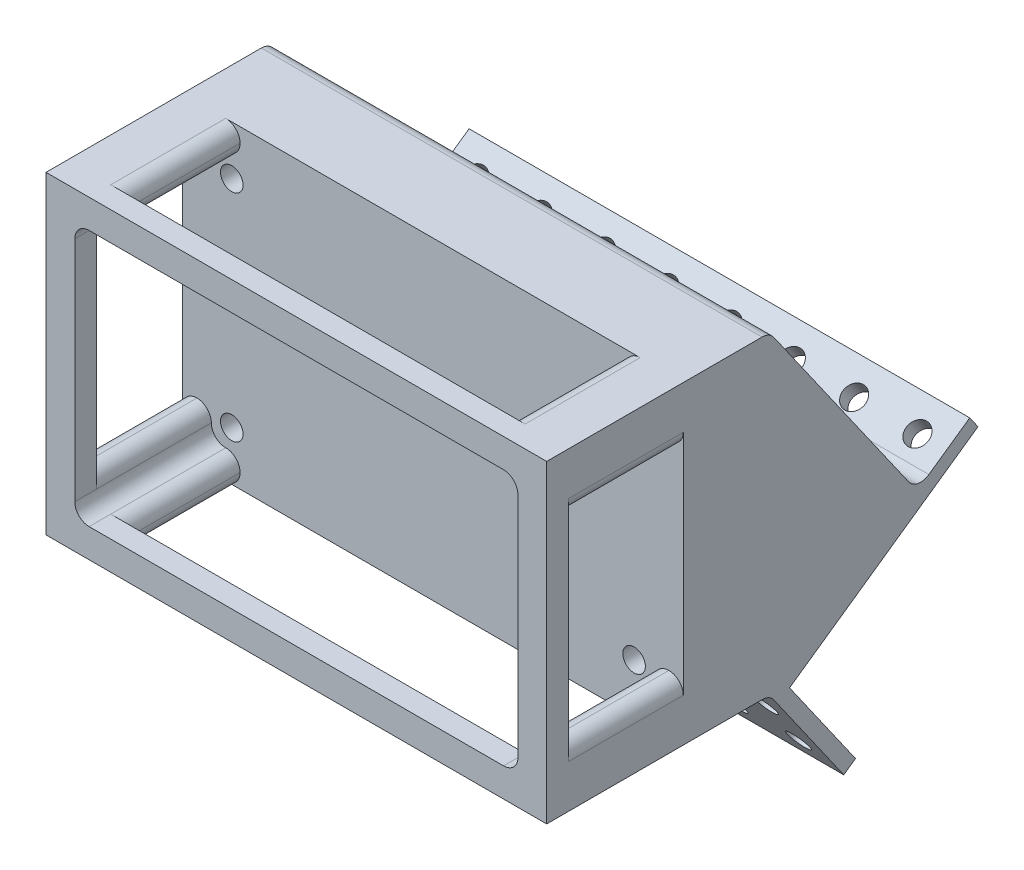
SolidWorks part; units mm, degrees
material "PET"
ref_plane "Front Plane" through (0, 0, 0) normal (0, 0, 1) x (1, 0, 0)
ref_plane "Top Plane" through (0, 0, 0) normal (0, 1, 0) x (1, 0, 0)
ref_plane "Right Plane" through (0, 0, 0) normal (1, 0, 0) x (0, 0, -1)
sketch "Sketch1" plane through (0, 0, 0) normal (0, 0, 1) x (1, 0, 0)
  line L0 (-44.4246, 23.8125) -> (-44.4246, -23.8125) construction
  line L1 (-48.9331, -28.321) -> (48.9331, -28.321)
  line L2 (-48.9331, -28.321) -> (-48.9331, 28.321)
  line L3 (-48.9331, 28.321) -> (48.9331, 28.321)
  line L4 (48.9331, -28.321) -> (48.9331, 28.321)
  line L5 (-48.9331, -28.321) -> (48.9331, 28.321) construction
  line L6 (-48.9331, 28.321) -> (48.9331, -28.321) construction
  line L7 (-55.2831, -34.671) -> (55.2831, -34.671)
  line L8 (-55.2831, -34.671) -> (-55.2831, 34.671)
  line L9 (-55.2831, 34.671) -> (55.2831, 34.671)
  line L10 (55.2831, -34.671) -> (55.2831, 34.671)
  line L11 (-55.2831, -34.671) -> (55.2831, 34.671) construction
  line L12 (-55.2831, 34.671) -> (55.2831, -34.671) construction
  line L13 (0, 28.321) -> (0, -28.321) construction
  line L14 (-55.2831, -21.971) -> (-48.9331, -21.971)
  line L15 (-48.9331, -21.971) -> (-48.9331, -28.321)
  line L16 (-48.9331, -28.321) -> (-42.5831, -28.321)
  line L17 (-42.5831, -28.321) -> (-42.5831, -34.671)
  line L18 (42.5831, -28.321) -> (42.5831, -34.671)
  line L19 (48.9331, -28.321) -> (42.5831, -28.321)
  line L20 (48.9331, -21.971) -> (48.9331, -28.321)
  line L21 (55.2831, -21.971) -> (48.9331, -21.971)
  line L22 (-55.2831, 0) -> (55.2831, 0) construction
  line L23 (55.2831, 21.971) -> (48.9331, 21.971)
  line L24 (48.9331, 21.971) -> (48.9331, 28.321)
  line L25 (48.9331, 28.321) -> (42.5831, 28.321)
  line L26 (42.5831, 28.321) -> (42.5831, 34.671)
  line L27 (-42.5831, 28.321) -> (-42.5831, 34.671)
  line L28 (-48.9331, 28.321) -> (-42.5831, 28.321)
  line L29 (-48.9331, 21.971) -> (-48.9331, 28.321)
  line L30 (-55.2831, 21.971) -> (-48.9331, 21.971)
  circle A0 centre (-44.4246, -23.8125) radius 2.4892
  circle A1 centre (-44.4246, 23.8125) radius 2.4892
  circle A2 centre (44.4246, -23.8125) radius 2.4892
  circle A3 centre (44.4246, 23.8125) radius 2.4892
  point P0 (0, 0)
  point P6 (0, 0)
  point P11 (-48.9331, 0)
  point P16 (-44.4246, 0)
  dimension "D5" = 4.9784
  dimension "D1" = 97.8662
  dimension "D2" = 56.642
  dimension "D3" = 6.35
  dimension "D4" = 6.35
  dimension "D6" = 4.5085
  dimension "D7" = 12.7
  dimension "D8" = 47.625
  dimension "D9" = 12.7
extrude "Boss-Extrude1" add sketch "Sketch1" along normal mid plane 19.05 contours L30 L8 L14 L15 L16 L17 L7 L18 L19 L20 L21 L10 L23 L24 L25 L26 L9 L27 L28 L29 A2 A1 A0 A3 | L8 L30 L29 L28 L27 L9 | L26 L25 L24 L23 L10 L9 | L10 L21 L20 L19 L18 L7 | L17 L16 L15 L14 L8 L7 | L30 L8 L14 L2 | L27 L3 L26 L9 | L10 L23 L4 L21 | L18 L1 L17 L7 | A0 | A1 | A3 | A2 region at (0, 0, 0) region at (-49.9914, -29.3793, 0) region at (0, -31.496, 0) region at (-52.1081, 0, 0) region at (49.9914, -29.3793, 0) region at (-49.9914, 29.3793, 0) region at (52.1081, 0, 0) region at (0, 31.496, 0) region at (49.9914, 29.3793, 0) region at (-44.4246, -23.8125, 0) region at (-44.4246, 23.8125, 0) region at (44.4246, -23.8125, 0) region at (44.4246, 23.8125, 0)
extrude "Boss-Extrude2" add sketch "Sketch1<3>" along normal blind 34.925 contours L8 L30 L29 L28 L27 L9 | L26 L25 L24 L23 L10 L9 | L17 L16 L15 L14 L8 L7 | L10 L21 L20 L19 L18 L7 region at (-49.9914, -29.3793, 0) region at (49.9914, -29.3793, 0) region at (-49.9914, 29.3793, 0) region at (49.9914, 29.3793, 0)
sketch "Sketch1<3>" plane through (0, 0, 0) normal (0, 0, 1) x (1, 0, 0) same geometry as "Sketch1"
extrude "Boss-Extrude3" add sketch "Sketch1<5>" along normal blind 4.7625 from surface contours L27 L3 L26 L9 | L26 L3 L4 L23 L10 L9 | L10 L23 L4 L21 | L10 L21 L4 L1 L18 L7 | L18 L1 L17 L7 | L17 L1 L2 L14 L8 L7 | L30 L8 L14 L2 | L8 L30 L2 L3 L27 L9 region at (-49.9914, -29.3793, 0) region at (0, -31.496, 0) region at (-52.1081, 0, 0) region at (49.9914, -29.3793, 0) region at (-49.9914, 29.3793, 0) region at (52.1081, 0, 0) region at (0, 31.496, 0) region at (49.9914, 29.3793, 0) starting at face at (-48.9331, 28.321, 34.925)
sketch "Sketch1<5>" plane through (0, 0, 0) normal (0, 0, 1) x (1, 0, 0) same geometry as "Sketch1"
sketch "Sketch2" plane through (0, 0, 0) normal (1, 0, 0) x (0, 0, -1)
  line L0 (9.525, 34.671) -> (9.525, -34.671)
  line L2 (9.525, 34.671) -> (42.1051, -11.8582)
  line L3 (55.5598, -6.313) -> (13.9469, -35.4507)
  line L4 (9.525, -34.671) -> (25.9149, -58.0783)
  line L5 (25.9149, -58.0783) -> (28.5158, -56.2572)
  line L6 (28.5158, -56.2572) -> (13.9469, -35.4507)
  line L8 (55.5598, -6.313) -> (53.7387, -3.7122)
  line L9 (53.7387, -3.7122) -> (42.1051, -11.8582)
  line L10 (9.525, -34.671) -> (9.525, 34.671) construction
  point P6 (9.525, 34.2254)
  dimension "D1" = 3.175
  dimension "D2" = 55
  dimension "D3" = 25.4
  dimension "D4" = 3.175
  dimension "D5" = 50.8
extrude "Boss-Extrude4" add sketch "Sketch2" along normal up to surface (55.2831 mm away) and the other way up to surface (55.2831 mm away) up to face at (55.2831, 0, 15.0813) other way up to face at (-55.2831, 0, 15.0813)
extrude "Cut-Extrude3" cut sketch "Sketch1<6>" against normal through all both and the other way through all contours A1 | A3 | A2 | A0 region at (-44.4246, -23.8125, 0) region at (-44.4246, 23.8125, 0) region at (44.4246, -23.8125, 0) region at (44.4246, 23.8125, 0)
sketch "Sketch1<6>" plane through (0, 0, 0) normal (0, 0, 1) x (1, 0, 0) same geometry as "Sketch1"
sketch "Sketch3" plane through (0, -6.9311, 9.8987) normal (0, -0.5736, 0.8192) x (1, 0, 0)
  line L0 (-55.2831, -33.8641) -> (-55.2831, -62.4391) construction
  line L1 (55.2831, -62.4391) -> (-55.2831, -62.4391) construction
  line L2 (55.2831, -62.4391) -> (55.2831, -33.8641) construction
  circle A0 centre (-48.9331, -56.0891) radius 2.4892
  circle A1 centre (-34.9522, -56.0891) radius 2.4892
  circle A2 centre (-20.9713, -56.0891) radius 2.4892
  circle A3 centre (-6.9904, -56.0891) radius 2.4892
  circle A4 centre (6.9904, -56.0891) radius 2.4892
  circle A5 centre (20.9713, -56.0891) radius 2.4892
  circle A6 centre (34.9522, -56.0891) radius 2.4892
  circle A7 centre (48.9331, -56.0891) radius 2.4892
  circle A8 centre (-34.9522, -43.3891) radius 2.4892
  circle A9 centre (-20.9713, -43.3891) radius 2.4892
  circle A10 centre (-6.9904, -43.3891) radius 2.4892
  circle A11 centre (6.9904, -43.3891) radius 2.4892
  circle A12 centre (20.9713, -43.3891) radius 2.4892
  circle A13 centre (34.9522, -43.3891) radius 2.4892
  circle A14 centre (48.9331, -43.3891) radius 2.4892
  circle A15 centre (-48.9331, -43.3891) radius 2.4892
  dimension "D3" = 4.9784
  dimension "D1" = 6.35
  dimension "D2" = 6.35
  dimension "D6" = 6.35
  dimension "D7" = 12.7
  dimension "D4" = 8
  dimension "D5" = 2
extrude "Cut-Extrude1" cut sketch "Sketch3" against normal through all both
sketch "Sketch4" plane through (0, -27.7399, -19.4237) normal (0, 0.8192, 0.5736) x (1, 0, 0)
  line L0 (55.2831, 41.891) -> (-55.2831, 41.891) construction
  line L1 (55.2831, 27.6889) -> (55.2831, 41.891) construction
  line L2 (-55.2831, 41.891) -> (-55.2831, 27.6889) construction
  circle A0 centre (48.9331, 35.541) radius 2.4892
  circle A1 centre (34.9522, 35.541) radius 2.4892
  circle A2 centre (20.9713, 35.541) radius 2.4892
  circle A3 centre (6.9904, 35.541) radius 2.4892
  circle A4 centre (-6.9904, 35.541) radius 2.4892
  circle A5 centre (-20.9713, 35.541) radius 2.4892
  circle A6 centre (-34.9522, 35.541) radius 2.4892
  circle A7 centre (-48.9331, 35.541) radius 2.4892
  dimension "D5" = 4.9784
  dimension "D1" = 6.35
  dimension "D2" = 6.35
  dimension "D4" = 6.35
  dimension "D3" = 8
extrude "Cut-Extrude2" cut sketch "Sketch4" against normal through all both
fillet "Fillet1" radius 3.175 3 edges at (0, 34.671, -9.525) (0, -34.671, -9.525) (0, -11.8582, -42.1051)
fillet "Fillet2" radius 3.175 20 edges at (48.9331, -28.321, 24.6062) (42.5831, -28.321, 22.225) (-42.5831, -28.321, 22.225) (-48.9331, -28.321, 24.6062) (-48.9331, 21.971, 22.225) (-48.9331, 28.321, 24.6062) (-42.5831, 28.321, 22.225) (42.5831, 28.321, 22.225) (48.9331, 28.321, 24.6062) (48.9331, 21.971, 22.225) (48.9331, -21.971, 22.225) (-48.9331, -21.971, 22.225) (55.2831, 21.971, 22.225) (-42.5831, -34.671, 22.225) (42.5831, -34.671, 22.225) (55.2831, -21.971, 22.225) (-55.2831, -21.971, 22.225) (-55.2831, 21.971, 22.225) (-42.5831, 34.671, 22.225) (42.5831, 34.671, 22.225)
